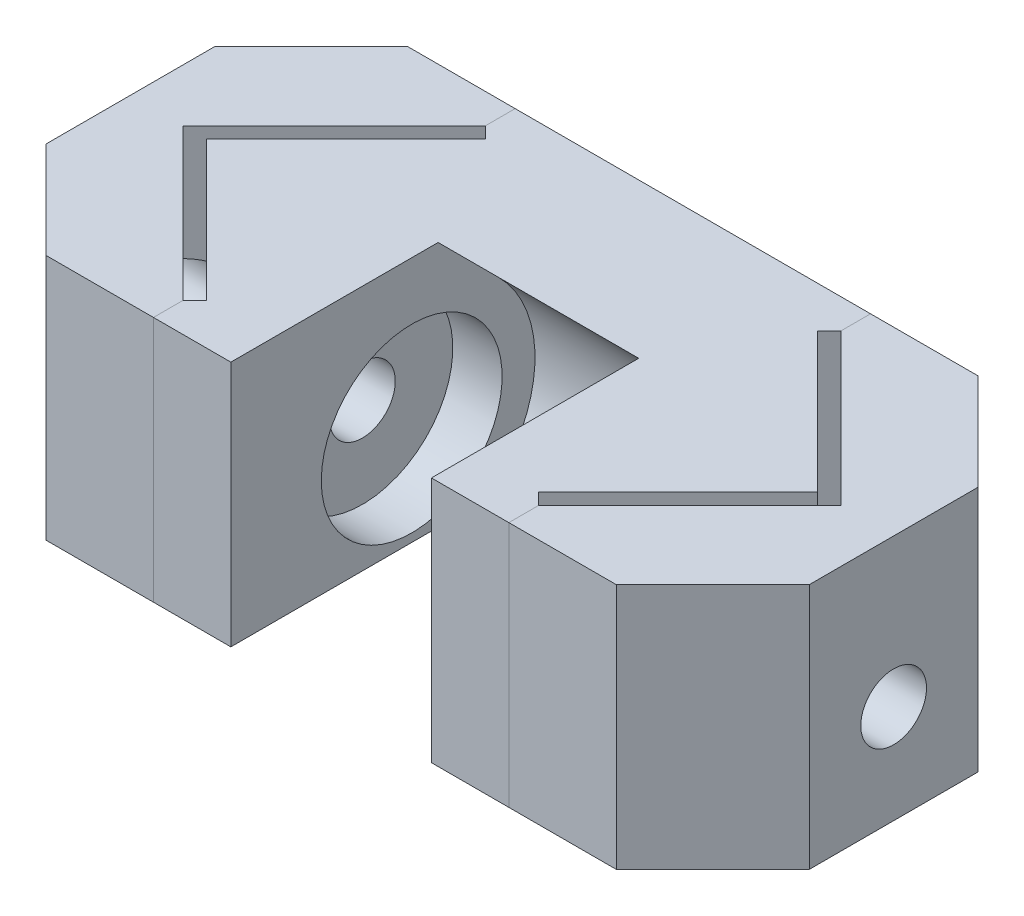
SolidWorks part; units mm, degrees
ref_plane "Front Plane" through (0, 0, 0) normal (0, 0, 1) x (1, 0, 0)
ref_plane "Top Plane" through (0, 0, 0) normal (0, 1, 0) x (1, 0, 0)
ref_plane "Right Plane" through (0, 0, 0) normal (1, 0, 0) x (0, 0, -1)
sketch "Sketch2" plane through (0, 0, 0) normal (0, 1, 0) x (1, 0, 0)
  line L0 (0, 0) -> (40, 0) construction
  line L1 (40, 0) -> (21.6152, 18.3848)
  line L2 (21.6152, 18.3848) -> (20.201, 16.9706)
  line L3 (20.201, 16.9706) -> (37.1716, 0)
  line L4 (20.201, -16.9706) -> (37.1716, 0)
  line L5 (21.6152, -18.3848) -> (20.201, -16.9706)
  line L6 (40, 0) -> (21.6152, -18.3848)
  line L8 (-10, 21.05) -> (10, 21.05)
  line L9 (-10, 21.05) -> (-10, -21.05)
  line L10 (-10, -21.05) -> (10, -21.05)
  line L11 (10, 21.05) -> (10, -21.05)
  line L12 (-10, 21.05) -> (10, -21.05) construction
  line L13 (-10, -21.05) -> (10, 21.05) construction
  line L14 (11.2, 11) -> (18.2, 11) construction
  line L15 (11.2, 11) -> (11.2, -11) construction
  line L16 (11.2, -11) -> (18.2, -11) construction
  line L17 (18.2, 11) -> (18.2, -11) construction
  point P12 (15.201, 0)
  dimension "D1" = 40
  dimension "D2" = 26
  dimension "D3" = 2
  dimension "D4" = 135
  dimension "D5" = 20
  dimension "D6" = 22
  dimension "D7" = 7
  dimension "D8" = 2.4
sketch "Sketch3" plane through (0, 0, 0) normal (0, 1, 0) x (1, 0, 0)
  line L0 (37.1716, 0) -> (20.201, 16.9706)
  line L1 (20.201, 16.9706) -> (21.6152, 18.3848)
  line L2 (21.6152, 18.3848) -> (21.6152, 22)
  line L3 (21.6152, 22) -> (12.2, 22)
  line L4 (12.2, 0) -> (12.2, -22)
  line L5 (0, 0) -> (40, 0) construction
  line L6 (18.2, 11) -> (18.2, -11) construction
  line L7 (12.2, 0) -> (37.1716, 0) construction
  line L8 (21.6152, -22) -> (12.2, -22)
  line L9 (21.6152, -18.3848) -> (21.6152, -22)
  line L10 (20.201, -16.9706) -> (21.6152, -18.3848)
  line L11 (37.1716, 0) -> (20.201, -16.9706)
  line L12 (12.2, 22) -> (-12.2, 22)
  line L13 (0, 22) -> (0, 0) construction
  line L14 (-12.2, 0) -> (12.2, 0)
  line L15 (-12.2, 0) -> (-37.1716, 0) construction
  line L16 (-37.1716, 0) -> (-20.201, -16.9706)
  line L17 (-20.201, -16.9706) -> (-21.6152, -18.3848)
  line L18 (-21.6152, -18.3848) -> (-21.6152, -22)
  line L19 (-21.6152, -22) -> (-12.2, -22)
  line L20 (-12.2, 0) -> (-12.2, -22)
  line L21 (-21.6152, 22) -> (-12.2, 22)
  line L22 (-21.6152, 18.3848) -> (-21.6152, 22)
  line L23 (-20.201, 16.9706) -> (-21.6152, 18.3848)
  line L24 (-37.1716, 0) -> (-20.201, 16.9706)
  dimension "D1" = 22
  dimension "D2" = 6
extrude "Boss-Extrude1" add sketch "Sketch3" along normal mid plane 30
sketch "Sketch4" plane through (0, 0, 0) normal (0, 1, 0) x (1, 0, 0)
  line L0 (21.6152, 18.3848) -> (21.6152, 22)
  line L1 (21.6152, 22) -> (34.6871, 22)
  line L2 (34.6871, 22) -> (46.4237, 10.2634)
  line L3 (46.4237, 10.2634) -> (46.4237, -10.2634)
  line L4 (40, 0) -> (21.6152, 18.3848)
  line L5 (40, 0) -> (46.4237, 0) construction
  line L6 (40, 0) -> (21.6152, -18.3848)
  line L7 (34.6871, -22) -> (46.4237, -10.2634)
  line L8 (21.6152, -22) -> (34.6871, -22)
  line L9 (21.6152, -18.3848) -> (21.6152, -22)
extrude "Boss-Extrude2" add sketch "Sketch4" along normal mid plane 30 separate body
sketch "Sketch5" plane through (0, 0, 0) normal (-1, 0, 0) x (0, 0, 1)
  line L0 (0, 0) -> (0, -3) construction
  circle A0 centre (0, -3) radius 11
  circle A1 centre (0, -3) radius 4
  dimension "D2" = 22
  dimension "D3" = 8
  dimension "D1" = 3
extrude "Cut-Extrude1" cut sketch "Sketch5" against normal mid plane 36.4
extrude "Cut-Extrude2" cut sketch "Sketch5<2>" against normal through all both and the other way through all contours A1 region at (0, -3, 0)
sketch "Sketch5<2>" plane through (0, 0, 0) normal (-1, 0, 0) x (0, 0, 1) same geometry as "Sketch5"
sketch "Sketch7" plane through (0, 0, 0) normal (1, 0, 0) x (0, 0, -1)
  line L0 (-4.2963, 22.5095) -> (10.6066, 7.6066)
  line L1 (24.2, 0) -> (-24.2, 0) construction
  line L2 (0, -3) -> (28.5514, -3) construction
  line L3 (-4.2963, -28.5095) -> (10.6066, -13.6066)
  line L4 (-4.2963, 22.5095) -> (-27.9446, 22.5095)
  line L5 (-27.9446, 22.5095) -> (-27.9446, -28.5095)
  line L6 (-27.9446, -28.5095) -> (-4.2963, -28.5095)
  circle A0 centre (0, -3) radius 15
  dimension "D1" = 30
  dimension "D2" = 45
extrude "Cut-Extrude3" cut sketch "Sketch7" along direction (1, 0, 0) on the side of the normal up to surface (12.2 mm away) from surface contours A0 L0 L4 L5 L6 L3 | A0 region at (0, -3, 15.8855) region at (0, -3, 0) up to face at (12.2, -1, 9.1667) starting at face at (-12.2, -1, 9.1667)
mirror "Mirror1" about plane through (0, 0, 0) normal (1, 0, 0) of bodies 104
